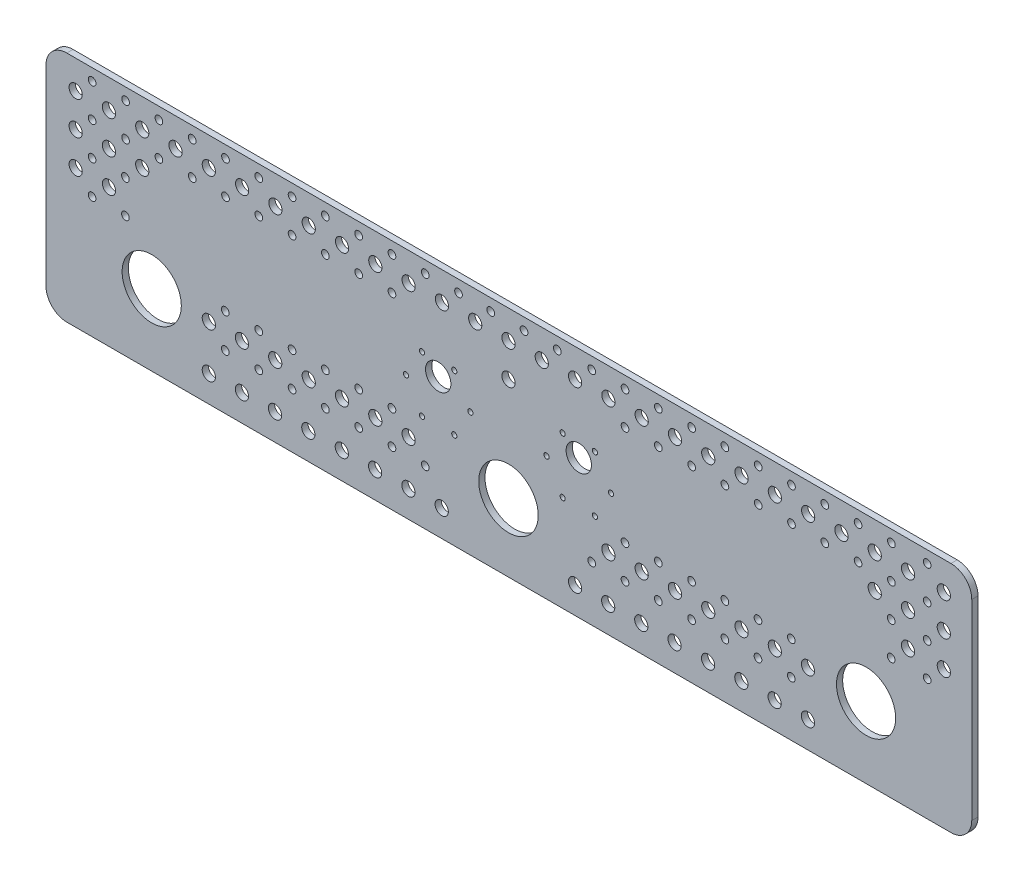
SolidWorks part; units mm, degrees
ref_plane "Front" through (0, 0, 0) normal (0, 0, 1) x (1, 0, 0)
ref_plane "Top" through (0, 0, 0) normal (0, 1, 0) x (1, 0, 0)
ref_plane "Right" through (0, 0, 0) normal (1, 0, 0) x (0, 0, -1)
sketch "Sketch1" plane through (0, 0, 0) normal (0, 0, 1) x (1, 0, 0)
  line L1 (-435.1498, 91.0845) -> (-10.2738, 91.0845)
  line L2 (-445.1498, 81.0845) -> (-445.1498, -10.9155)
  line L3 (-435.1498, -20.9155) -> (-10.2738, -20.9155)
  line L4 (-0.2738, 81.0845) -> (-0.2738, -10.9155)
  circle A0 centre (-394.3498, 13.3845) radius 14.225
  circle A1 centre (-51.0738, 13.3845) radius 14.225
  circle A11 centre (-222.8998, 11.8845) radius 14.3
  circle A20 centre (-30.8998, 61.3845) radius 3.18
  circle A21 centre (-414.8998, 61.3845) radius 3.18
  circle A23 centre (-286.8998, 13.3845) radius 3.18
  arc A24 (-10.2738, -20.9155) -> (-0.2738, -10.9155) centre (-10.2738, -10.9155) ccw
  arc A25 (-435.1498, -20.9155) -> (-445.1498, -10.9155) centre (-435.1498, -10.9155) cw
  arc A26 (-435.1498, 91.0845) -> (-445.1498, 81.0845) centre (-435.1498, 81.0845) ccw
  arc A27 (-10.2738, 91.0845) -> (-0.2738, 81.0845) centre (-10.2738, 81.0845) cw
  circle A28 centre (-302.8998, 13.3845) radius 3.18
  circle A29 centre (-318.8998, 13.3845) radius 3.18
  circle A30 centre (-270.8998, 13.3845) radius 3.18
  circle A45 centre (-310.8998, 5.3845) radius 1.85
  circle A46 centre (-294.8998, 5.3845) radius 1.85
  circle A47 centre (-278.8998, 5.3845) radius 1.85
  circle A48 centre (-262.8998, 5.3845) radius 1.85
  circle A49 centre (-310.8998, 21.3845) radius 1.85
  circle A50 centre (-294.8998, 21.3845) radius 1.85
  circle A51 centre (-278.8998, 21.3845) radius 1.85
  circle A53 centre (-158.8998, 13.3845) radius 3.18
  circle A54 centre (-174.8998, 13.3845) radius 3.18
  circle A56 centre (-142.8998, 13.3845) radius 3.18
  circle A57 centre (-126.8998, 13.3845) radius 3.18
  circle A58 centre (-182.8998, 5.3845) radius 1.85
  circle A59 centre (-166.8998, 5.3845) radius 1.85
  circle A60 centre (-150.8998, 5.3845) radius 1.85
  circle A61 centre (-134.8998, 5.3845) radius 1.85
  circle A63 centre (-166.8998, 21.3845) radius 1.85
  circle A64 centre (-150.8998, 21.3845) radius 1.85
  circle A65 centre (-134.8998, 21.3845) radius 1.85
  circle A66 centre (-318.8998, 77.3845) radius 3.18
  circle A67 centre (-334.8998, 77.3845) radius 3.18
  circle A68 centre (-334.8998, 77.3845) radius 3.18
  circle A69 centre (-302.8998, 77.3845) radius 3.18
  circle A70 centre (-286.8998, 77.3845) radius 3.18
  circle A71 centre (-310.8998, 69.3845) radius 1.85
  circle A72 centre (-294.8998, 69.3845) radius 1.85
  circle A73 centre (-278.8998, 69.3845) radius 1.85
  circle A75 centre (-310.8998, 85.3845) radius 1.85
  circle A76 centre (-294.8998, 85.3845) radius 1.85
  circle A77 centre (-278.8998, 85.3845) radius 1.85
  circle A78 centre (-262.8998, 85.3845) radius 1.85
  circle A79 centre (-270.8998, 77.3845) radius 3.18
  circle A80 centre (-142.8998, 77.3845) radius 3.18
  circle A81 centre (-158.8998, 77.3845) radius 3.18
  circle A82 centre (-174.8998, 77.3845) radius 3.18
  circle A83 centre (-126.8998, 77.3845) radius 3.18
  circle A84 centre (-110.8998, 77.3845) radius 3.18
  circle A86 centre (-166.8998, 69.3845) radius 1.85
  circle A87 centre (-150.8998, 69.3845) radius 1.85
  circle A88 centre (-134.8998, 69.3845) radius 1.85
  circle A89 centre (-182.8998, 85.3845) radius 1.85
  circle A90 centre (-166.8998, 85.3845) radius 1.85
  circle A91 centre (-150.8998, 85.3845) radius 1.85
  circle A92 centre (-134.8998, 85.3845) radius 1.85
  circle A94 centre (-222.8998, 77.3845) radius 3.18
  circle A95 centre (-238.8998, 77.3845) radius 3.18
  circle A96 centre (-254.8998, 77.3845) radius 3.18
  circle A97 centre (-206.8998, 77.3845) radius 3.18
  circle A98 centre (-190.8998, 77.3845) radius 3.18
  circle A103 centre (-246.8998, 85.3845) radius 1.85
  circle A104 centre (-231.4272, 85.3845) radius 1.85
  circle A105 centre (-215.4272, 85.3845) radius 1.85
  circle A106 centre (-199.4272, 85.3845) radius 1.85
  circle A107 centre (-398.8998, 77.3845) radius 3.18
  circle A108 centre (-414.8998, 77.3845) radius 3.18
  circle A109 centre (-382.8998, 77.3845) radius 3.18
  circle A110 centre (-366.8998, 77.3845) radius 3.18
  circle A111 centre (-390.8998, 69.3845) radius 1.85
  circle A112 centre (-374.8998, 69.3845) radius 1.85
  circle A113 centre (-358.8998, 69.3845) radius 1.85
  circle A114 centre (-342.8998, 69.3845) radius 1.85
  circle A115 centre (-390.8998, 85.3845) radius 1.85
  circle A116 centre (-374.8998, 85.3845) radius 1.85
  circle A117 centre (-358.8998, 85.3845) radius 1.85
  circle A118 centre (-342.8998, 85.3845) radius 1.85
  circle A119 centre (-350.8998, 77.3845) radius 3.18
  circle A120 centre (-78.8998, 77.3845) radius 3.18
  circle A121 centre (-94.8998, 77.3845) radius 3.18
  circle A122 centre (-62.8998, 77.3845) radius 3.18
  circle A123 centre (-46.8998, 77.3845) radius 3.18
  circle A124 centre (-86.8998, 69.3845) radius 1.85
  circle A125 centre (-70.8998, 69.3845) radius 1.85
  circle A126 centre (-54.8998, 69.3845) radius 1.85
  circle A127 centre (-38.8998, 69.3845) radius 1.85
  circle A128 centre (-86.8998, 85.3845) radius 1.85
  circle A129 centre (-70.8998, 85.3845) radius 1.85
  circle A130 centre (-54.8998, 85.3845) radius 1.85
  circle A131 centre (-38.8998, 85.3845) radius 1.85
  circle A132 centre (-30.8998, 77.3845) radius 3.18
  circle A133 centre (-430.8998, 77.3845) radius 3.18
  circle A134 centre (-430.8998, 61.3845) radius 3.18
  circle A135 centre (-422.9957, 69.3845) radius 1.85
  circle A136 centre (-406.8998, 69.3845) radius 1.85
  circle A137 centre (-422.9957, 85.3845) radius 1.85
  circle A138 centre (-406.8998, 85.3845) radius 1.85
  circle A139 centre (-13.7008, 61.3845) radius 3.18
  circle A140 centre (-21.7008, 69.3845) radius 1.85
  circle A141 centre (-21.7008, 85.3845) radius 1.85
  circle A142 centre (-13.7008, 77.3845) radius 3.18
  circle A143 centre (-118.8998, 69.3845) radius 1.85
  circle A144 centre (-102.8998, 69.3845) radius 1.85
  circle A145 centre (-118.8998, 85.3845) radius 1.85
  circle A146 centre (-102.8998, 85.3845) radius 1.85
  circle A147 centre (-326.8998, 69.3845) radius 1.85
  circle A148 centre (-326.8998, 85.3845) radius 1.85
  circle A149 centre (-334.9957, 13.3845) radius 3.18
  circle A150 centre (-350.9957, 13.3845) radius 3.18
  circle A151 centre (-366.8998, 13.3845) radius 3.18
  circle A152 centre (-358.9957, 5.3845) radius 1.85
  circle A153 centre (-342.8998, 5.3845) radius 1.85
  circle A154 centre (-326.8998, 5.3845) radius 1.85
  circle A155 centre (-358.9957, 21.7191) radius 1.85
  circle A156 centre (-342.8998, 21.7191) radius 1.85
  circle A157 centre (-326.8998, 21.7191) radius 1.85
  circle A158 centre (-110.8998, 13.3845) radius 3.18
  circle A159 centre (-94.8998, 13.3845) radius 3.18
  circle A160 centre (-78.9957, 13.3845) radius 3.18
  circle A161 centre (-118.8998, 5.3845) radius 1.85
  circle A162 centre (-102.9957, 5.3845) radius 1.85
  circle A163 centre (-86.9957, 5.3845) radius 1.85
  circle A164 centre (-118.8998, 21.3845) radius 1.85
  circle A165 centre (-102.9957, 21.3845) radius 1.85
  circle A166 centre (-86.9957, 21.3845) radius 1.85
  circle A167 centre (-422.9957, 37.3845) radius 1.85
  circle A168 centre (-406.9957, 37.3845) radius 1.85
  circle A169 centre (-422.9957, 53.3845) radius 1.85
  circle A170 centre (-406.9957, 53.3845) radius 1.85
  circle A171 centre (-38.9957, 37.3845) radius 1.85
  circle A172 centre (-38.9957, 53.3845) radius 1.85
  circle A173 centre (-21.7008, 37.3845) radius 1.85
  circle A174 centre (-21.7008, 53.3845) radius 1.85
  circle A175 centre (-398.8998, 61.3845) radius 3.18
  circle A176 centre (-414.8998, 45.3845) radius 3.18
  circle A177 centre (-430.8998, 45.3845) radius 3.18
  circle A178 centre (-46.8998, 61.3845) radius 3.18
  circle A179 centre (-30.8998, 45.3845) radius 3.18
  circle A180 centre (-13.7008, 45.3845) radius 3.18
  circle A181 centre (-366.8998, -8.1755) radius 3.18
  circle A182 centre (-270.9957, -8.1755) radius 3.18
  circle A183 centre (-286.9957, -8.1755) radius 3.18
  circle A184 centre (-302.9957, -8.1755) radius 3.18
  circle A185 centre (-254.9957, -8.1755) radius 3.18
  circle A186 centre (-319.0916, -8.1755) radius 3.18
  circle A187 centre (-335.0916, -8.1755) radius 3.18
  circle A188 centre (-350.9957, -8.1755) radius 3.18
  circle A189 centre (-190.8998, -8.1755) radius 3.18
  circle A190 centre (-94.9957, -8.1755) radius 3.18
  circle A191 centre (-110.9957, -8.1755) radius 3.18
  circle A192 centre (-126.9957, -8.1755) radius 3.18
  circle A193 centre (-78.9957, -8.1755) radius 3.18
  circle A194 centre (-143.0916, -8.1755) radius 3.18
  circle A195 centre (-159.0916, -8.1755) radius 3.18
  circle A196 centre (-174.9957, -8.1755) radius 3.18
  circle A199 centre (-189.1178, 45.6665) radius 6.1
  circle A212 centre (-256.6818, 45.6665) radius 6.1
  circle A237 centre (-264.4318, 52.0899) radius 1.25
  circle A238 centre (-248.9318, 52.0899) radius 1.25
  circle A239 centre (-241.1818, 38.6665) radius 1.25
  circle A240 centre (-248.9318, 25.2431) radius 1.25
  circle A241 centre (-264.4318, 25.2431) radius 1.25
  circle A242 centre (-272.1818, 38.6665) radius 1.25
  circle A243 centre (-181.3678, 25.2431) radius 1.25
  circle A244 centre (-173.6178, 38.6665) radius 1.25
  circle A245 centre (-181.3678, 52.0899) radius 1.25
  circle A246 centre (-196.8678, 52.0899) radius 1.25
  circle A247 centre (-204.6178, 38.6665) radius 1.25
  circle A248 centre (-196.8678, 25.2431) radius 1.25
  circle A249 centre (-222.8998, 61.3845) radius 3.18
  point P45 (-0.2738, -20.9155)
  point P52 (-0.2738, 91.0845)
  point P237 (0, 0)
  dimension "D2" = 50.8
  dimension "D4" = 50.8
  dimension "D8" = 8
  dimension "D12" = 222.25
  dimension "D13" = 8
  dimension "D14" = 16
  dimension "D15" = 16
  dimension "D16" = 16
  dimension "D17" = 16
  dimension "D21" = 16
  dimension "D23" = 16
  dimension "D27" = 10
  dimension "D28" = 10
  dimension "D29" = 10
  dimension "D30" = 10
  dimension "D24" = 16
  dimension "D87" = 33.782
  dimension "D10" = 33.782
  dimension "D1" = 112
  dimension "D3" = 34.3
  dimension "D5" = 34.3
  dimension "D7" = 8
  dimension "D9" = 16
  dimension "D11" = 8
  dimension "D18" = 16
  dimension "D19" = 16
  dimension "D20" = 16
  dimension "D22" = 16
  dimension "D25" = 16
  dimension "D26" = 32.8
  dimension "D31" = 16
  dimension "D33" = 16
  dimension "D34" = 16
  dimension "D36" = 16
  dimension "D38" = 16
  dimension "D39" = 16
  dimension "D40" = 16
  dimension "D42" = 16
  dimension "D43" = 16
  dimension "D44" = 16
  dimension "D46" = 16
  dimension "D47" = 16
  dimension "D48" = 16
  dimension "D49" = 64
  dimension "D50" = 16
  dimension "D51" = 16
  dimension "D52" = 16
  dimension "D53" = 16
  dimension "D54" = 16
  dimension "D55" = 32
  dimension "D56" = 16
  dimension "D57" = 16
  dimension "D58" = 16
  dimension "D59" = 16
  dimension "D60" = 13.7
  dimension "D61" = 8
  dimension "D62" = 16
  dimension "D63" = 16
  dimension "D64" = 8
  dimension "D65" = 16
  dimension "D66" = 16
  dimension "D70" = 16
  dimension "D71" = 16
  dimension "D72" = 16
  dimension "D73" = 16
  dimension "D74" = 16
  dimension "D75" = 16
  dimension "D76" = 16
  dimension "D77" = 16
  dimension "D78" = 16
  dimension "D79" = 16
  dimension "D80" = 16
  dimension "D81" = 8
  dimension "D82" = 16
  dimension "D83" = 16
  dimension "D84" = 16
  dimension "D85" = 16
  dimension "D86" = 12.74
  dimension "D88" = 33.782
extrude "Boss-Extrude5" add sketch "Sketch1" along normal blind 3
